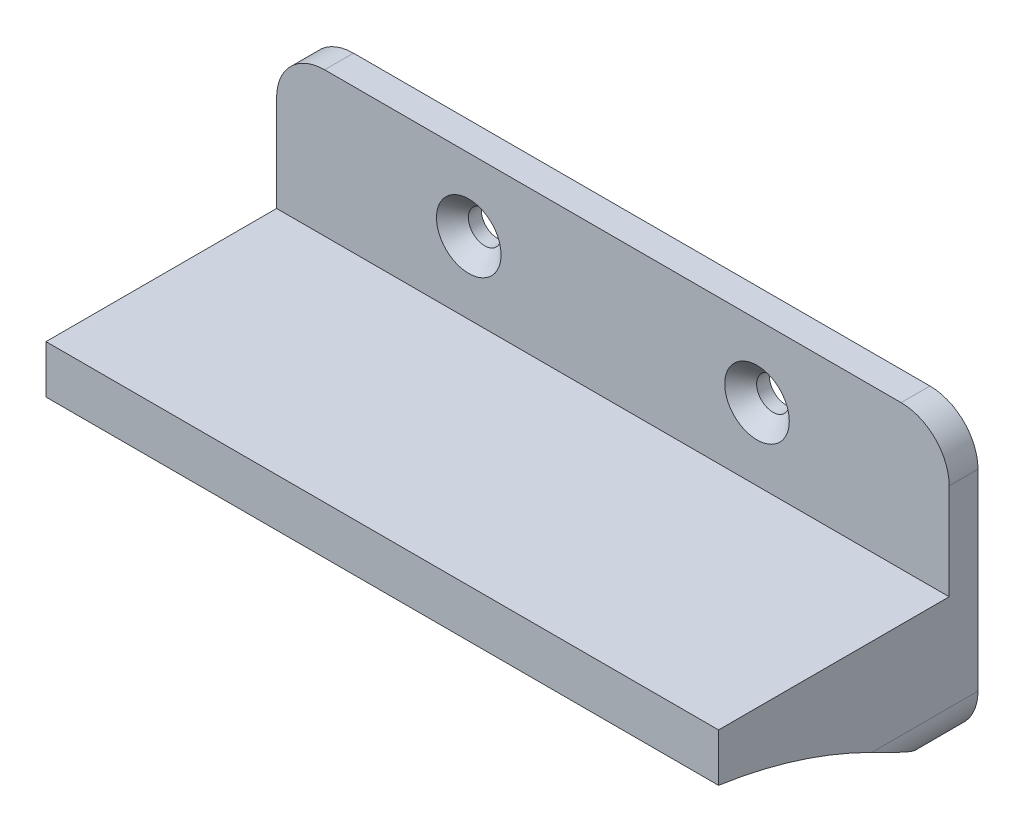
SolidWorks part; units mm, degrees
ref_plane "Alzado" through (0, 0, 0) normal (0, 0, 1) x (1, 0, 0)
ref_plane "Planta" through (0, 0, 0) normal (0, 1, 0) x (1, 0, 0)
ref_plane "Vista lateral" through (0, 0, 0) normal (1, 0, 0) x (0, 0, -1)
sketch "Croquis1" plane through (0, 0, 0) normal (0, 0, 1) x (1, 0, 0)
  line L1 (-29.9237, 15.4962) -> (40.0763, 15.4962)
  line L2 (-29.9237, 15.4962) -> (-29.9237, -14.5038)
  line L3 (-29.9237, -14.5038) -> (40.0763, -14.5038)
  line L4 (40.0763, 15.4962) -> (40.0763, -14.5038)
  dimension "D1" = 70
  dimension "D2" = 30
extrude "Saliente-Extruir1" add sketch "Croquis1" along normal blind 3
sketch "Croquis3" plane through (0, 0, 3) normal (0, 0, 1) x (1, 0, 0)
  line L0 (-29.9237, 15.4962) -> (-29.9237, -14.5038) construction
  line L1 (-29.9237, 0.4962) -> (40.0763, 0.4962)
  line L2 (-29.9237, 0.4962) -> (-29.9237, -4.5038)
  line L3 (-25.9237, -4.5038) -> (-7.9237, -4.5038)
  line L4 (40.0763, 0.4962) -> (40.0763, -4.5038)
  line L5 (40.0763, -14.5038) -> (40.0763, 15.4962) construction
  line L6 (-29.9237, -14.5038) -> (40.0763, -14.5038) construction
  line L7 (-7.9237, -4.5038) -> (-7.9237, -14.5038)
  line L9 (-29.9237, -4.5038) -> (-29.9237, -14.5038)
  line L10 (-29.9237, -14.5038) -> (-25.9237, -14.5038)
  line L11 (-25.9237, -4.5038) -> (-25.9237, -14.5038)
  line L13 (-3.9237, -4.5038) -> (-3.9237, -14.5038)
  line L14 (-7.9237, -14.5038) -> (-3.9237, -14.5038)
  line L15 (14.0763, -4.5038) -> (14.0763, -14.5038)
  line L17 (18.0763, -4.5038) -> (18.0763, -14.5038)
  line L18 (14.0763, -14.5038) -> (18.0763, -14.5038)
  line L19 (36.0763, -4.5038) -> (36.0763, -14.5038)
  line L21 (40.0763, -4.5038) -> (40.0763, -14.5038)
  line L22 (36.0763, -14.5038) -> (40.0763, -14.5038)
  line L23 (-3.9237, -4.5038) -> (14.0763, -4.5038)
  line L24 (18.0763, -4.5038) -> (36.0763, -4.5038)
  dimension "D1" = 5
  dimension "D2" = 10
  dimension "D3" = 4
  dimension "D4" = 4
extrude "Saliente-Extruir2" add sketch "Croquis3" along normal blind 24
sketch "Croquis4" plane through (-29.9237, 0, 0) normal (-1, 0, 0) x (0, 0, 1)
  line L0 (27, -14.5038) -> (27, -4.5038)
  line L1 (27, 0.4962) -> (27, -14.5038) construction
  line L2 (3, 0.4962) -> (3, -14.5038) construction
  line L3 (27, -14.5038) -> (0, -14.5038) construction
  line L4 (27, -14.5038) -> (3, -14.5038)
  arc A0 (3, -14.5038) -> (27, -4.5038) centre (34.43, -56.1358) cw
  dimension "D1" = 10
extrude "Cortar-Extruir1" cut sketch "Croquis4" against normal up to vertex (70 mm away) up to point (40.0763, 0.4962, 27)
sketch "Croquis5" plane through (0, 0, 3) normal (0, 0, 1) x (1, 0, 0)
  line L0 (-29.9237, 15.4962) -> (-29.9237, 0.4962) construction
  line L1 (5.0763, 15.4962) -> (5.0763, 0.4962) construction
  line L2 (40.0763, 15.4962) -> (-29.9237, 15.4962) construction
  line L3 (40.0763, 0.4962) -> (-29.9237, 0.4962) construction
  circle A0 centre (-9.9237, 7.9962) radius 1.5
  circle A1 centre (20.0763, 7.9962) radius 1.5
  circle A2 centre (-16.9237, -9.5038) radius 1.5
  circle A3 centre (27.0763, -9.5038) radius 1.5
  dimension "D1" = 20
  dimension "D2" = 3
extrude "Cortar-Extruir2" cut sketch "Croquis5" against normal up to vertex (3 mm away) up to point (-29.9237, 15.4962, 0)
hole_wizard "Refrentado para tornillo tapón con cabeza plana de clavija de M31" positions "Croquis6" profile "Croquis7" countersink size "M3" standard "Ansi Metric" end condition through all
sketch "Croquis6" plane through (0, 0, 3) normal (0, 0, 1) x (1, 0, 0)
  point P0 (-9.9237, 7.9962)
  point P3 (20.0763, 7.9962)
  point P6 (-16.9237, -9.5038)
  point P9 (27.0763, -9.5038)
sketch "Croquis7" plane through (-9.9237, 7.9962, 3) normal (1, 0, 0) x (0, -1, 0)
  line L0 (0, 0) -> (0, 3)
  line L1 (0, 3) -> (1.7, 3)
  line L2 (1.7, 3) -> (1.7, 1.66)
  line L3 (1.7, 1.66) -> (3.36, 0)
  line L5 (3.36, 0) -> (0, 0)
  line L6 (-1.7, 1.66) -> (-3.36, 0) construction
  line L11 (0, -6.35) -> (0, 107.95) construction
  dimension "Diámetro de taladro hasta el siguiente" = 3.4
  dimension "Profundidad de taladro hasta el siguiente" = 3
  dimension "Diámetro de avellanado cercano" = 6.72
  dimension "Ángulo de avellanado cercano" = 90
fillet "Redondeo1" radius 5 4 edges at (40.0763, -14.5038, 1.5) (-29.9237, -14.5038, 1.5) (40.0763, 15.4962, 1.5) (-29.9237, 15.4962, 1.5)
